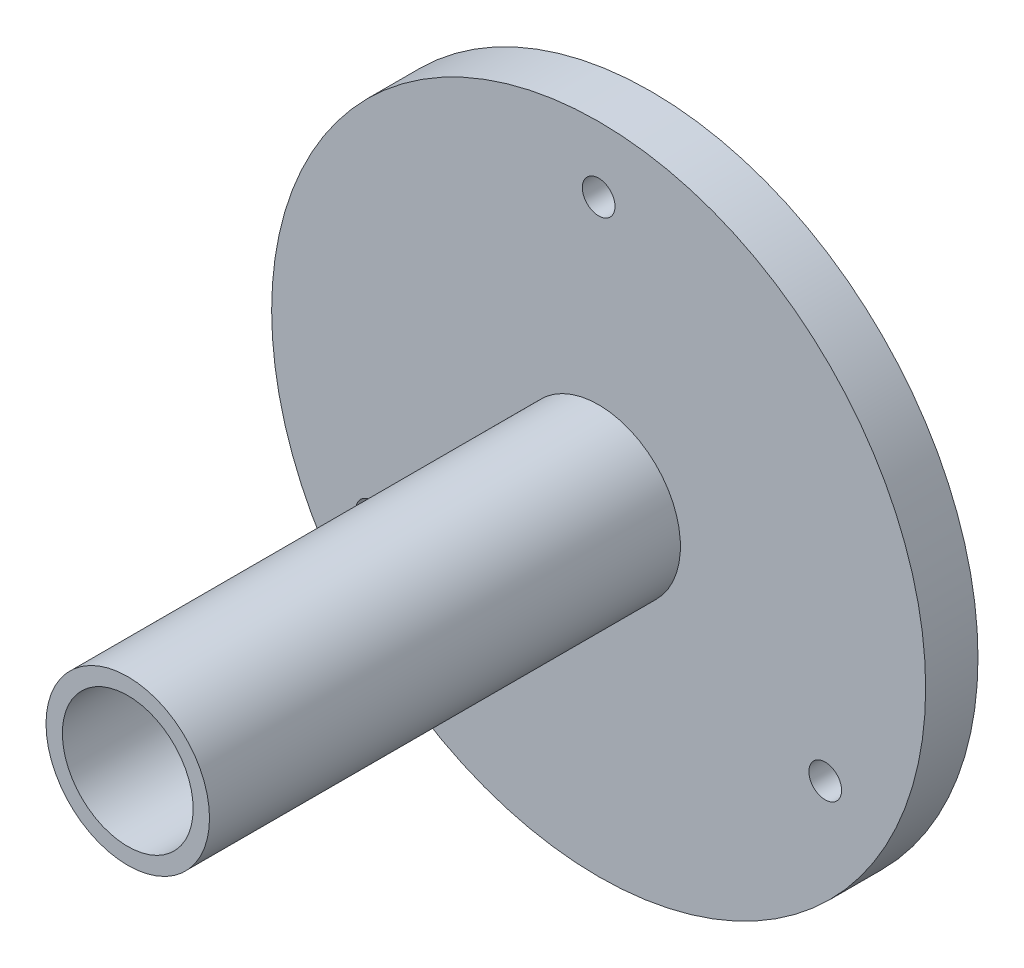
SolidWorks part; units mm, degrees
ref_plane "Front Plane" through (0, 0, 0) normal (0, 0, 1) x (1, 0, 0)
ref_plane "Top Plane" through (0, 0, 0) normal (0, 1, 0) x (1, 0, 0)
ref_plane "Right Plane" through (0, 0, 0) normal (1, 0, 0) x (0, 0, -1)
sketch "Sketch1" plane through (0, 0, 10) normal (0, 0, 1) x (1, 0, 0)
  circle A0 centre (0, 0) radius 10
  circle A1 centre (0, 0) radius 12.5
  dimension "D1" = 25
extrude "Boss-Extrude1" add sketch "Sketch1" along normal blind 80
sketch "Sketch2" plane through (0, 0, 10) normal (0, 0, -1) x (-1, 0, 0)
  circle A0 centre (0, 0) radius 50
  circle A1 centre (0, 0) radius 12.5
  dimension "D1" = 100
extrude "Boss-Extrude2" add sketch "Sketch2" against normal blind 8
sketch "Sketch3" plane through (0, 0, 18) normal (0, 0, 1) x (1, 0, 0)
  circle A0 centre (0, 40) radius 2.5
  circle A1 centre (0, 0) radius 50 construction
  dimension "D1" = 5
  dimension "D2" = 40
extrude "Cut-Extrude1" cut sketch "Sketch3" against normal blind 8
pattern_circular "CirPattern1" count 3 every 120 about axis through (0, 0, 18) along (0, 0, -1) of "Cut-Extrude1"
